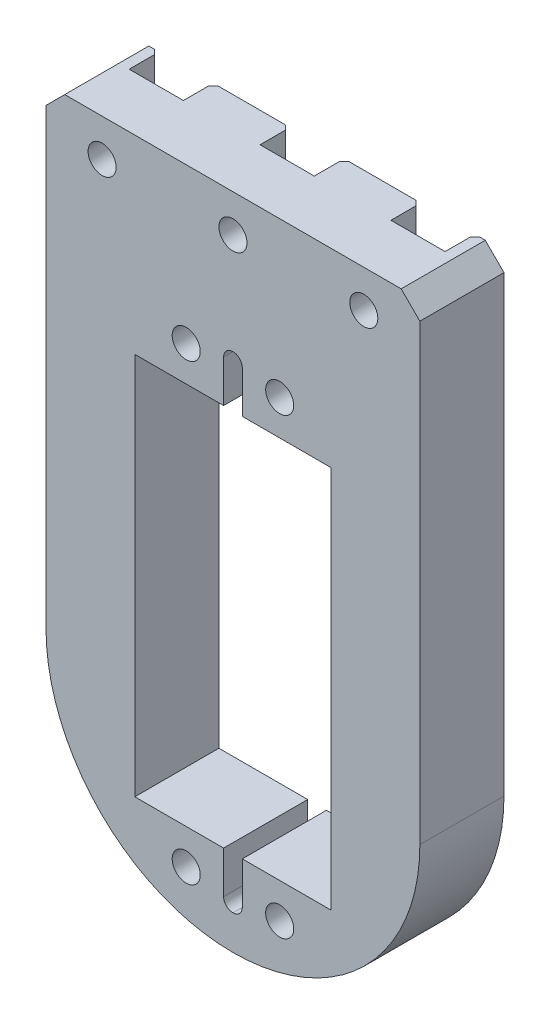
SolidWorks part; units mm, degrees
ref_plane "前视基准面" through (0, 0, 0) normal (0, 0, 1) x (1, 0, 0)
ref_plane "上视基准面" through (0, 0, 0) normal (0, 1, 0) x (1, 0, 0)
ref_plane "右视基准面" through (0, 0, 0) normal (1, 0, 0) x (0, 0, -1)
other "Configuration Table"
sketch "草图1" plane through (0, 0, 0) normal (0, 0, 1) x (1, 0, 0)
  line L1 (0, 0.5) -> (40, 0.5)
  line L2 (0, 0.5) -> (0, -70)
  line L3 (0, -70) -> (40, -70)
  line L4 (40, 0.5) -> (40, -70)
  dimension "D1" = 40
  dimension "D2" = 70.5
extrude "凸台-拉伸1" add sketch "草图1" along normal blind 9
chamfer "倒角1" distance 2 angle 45 2 edges at (40, 0.5, 4.5) (0, 0.5, 4.5)
fillet "圆角3" radius 20 2 edges at (0, -70, 4.5) (40, -70, 4.5)
sketch "草图2" plane through (0, 0, 0) normal (0, 0, -1) x (-1, 0, 0)
  line L0 (0, -1.5) -> (0, -50) construction
  line L1 (-30.5, -19.82) -> (-9.5, -19.82)
  line L2 (-30.5, -19.82) -> (-30.5, -60.82)
  line L3 (-30.5, -60.82) -> (-9.5, -60.82)
  line L4 (-9.5, -19.82) -> (-9.5, -60.82)
  line L5 (-30.5, -19.82) -> (-9.5, -60.82) construction
  line L6 (-30.5, -60.82) -> (-9.5, -19.82) construction
  point P0 (-20, -40.32)
  dimension "D1" = 21
  dimension "D2" = 41
  dimension "D3" = 20
  dimension "D4" = 29.68
extrude "切除-拉伸1" cut sketch "草图2" against normal blind 10
sketch "草图3" plane through (0, 0, 9) normal (0, 0, 1) x (1, 0, 0)
  line L0 (19, -14.32) -> (21, -14.32)
  line L1 (19, -14.32) -> (19, -19.82)
  line L2 (19, -19.82) -> (21, -19.82)
  line L3 (21, -14.32) -> (21, -19.82)
  line L4 (19, -14.32) -> (21, -19.82) construction
  line L5 (19, -19.82) -> (21, -14.32) construction
  line L6 (19, -60.82) -> (19, -66.32)
  line L7 (19, -60.82) -> (21, -60.82)
  line L8 (21, -60.82) -> (21, -66.32)
  line L9 (19, -66.32) -> (21, -66.32)
  line L10 (30.5, -19.82) -> (9.5, -19.82) construction
  line L11 (9.5, -19.82) -> (9.5, -60.82) construction
  line L12 (9.5, -60.82) -> (30.5, -60.82) construction
  point P0 (20, -17.07)
  dimension "D1" = 2
  dimension "D2" = 0
  dimension "D3" = 10.5
  dimension "D4" = 0
  dimension "D5" = 9.5
  dimension "D6" = 5.5
  dimension "D7" = 5.5
  dimension "D8" = 2
extrude "切除-拉伸2" cut sketch "草图3" against normal blind 10
sketch "草图4" plane through (0, 0, 0) normal (0, 0, -1) x (-1, 0, 0)
  line L0 (-21, -19.82) -> (-21, -14.32) construction
  line L1 (-21, -19.82) -> (-30.5, -19.82) construction
  circle A0 centre (-25, -16.07) radius 1.5
  circle A1 centre (-15, -16.07) radius 1.5
  circle A2 centre (-25, -64.57) radius 1.5
  circle A3 centre (-15, -64.57) radius 1.5
  dimension "D1" = 3
  dimension "D2" = 4
  dimension "D3" = 3.75
  dimension "D4" = 2
  dimension "D5" = 2
extrude "切除-拉伸3" cut sketch "草图4" against normal blind 10
sketch "草图5" plane through (0, 0, 0) normal (0, 0, -1) x (-1, 0, 0)
  line L0 (-38, 0.5) -> (-2, 0.5) construction
  line L1 (-40, -50) -> (-40, -1.5) construction
  circle A0 centre (-34, -3.5) radius 1.5
  circle A1 centre (-20, -3.5) radius 1.5
  circle A2 centre (-6, -3.5) radius 1.5
  dimension "D1" = 3
  dimension "D3" = 6
  dimension "D6" = 14
  dimension "D7" = 14
  dimension "D2" = 4
  dimension "D4" = 2
  dimension "D5" = 2
extrude "切除-拉伸4" cut sketch "草图5" against normal blind 10
fillet "圆角4" radius 1 4 edges at (21, -66.32, 4.5) (19, -66.32, 4.5) (21, -14.32, 4.5) (19, -14.32, 4.5)
sketch "草图7" plane through (0, 0, 0) normal (0, 0, -1) x (-1, 0, 0)
  line L2 (-36.9, -3.5) -> (-36.9, 0.5)
  line L3 (-36.9, 0.5) -> (-31.1, 0.5)
  line L4 (-31.1, -3.5) -> (-31.1, 0.5)
  line L5 (-17.1, -3.5) -> (-17.1, 0.5)
  line L6 (-22.9, 0.5) -> (-17.1, 0.5)
  line L7 (-22.9, -3.5) -> (-22.9, 0.5)
  line L8 (-3.1, -3.5) -> (-3.1, 0.5)
  line L9 (-8.9, 0.5) -> (-3.1, 0.5)
  line L10 (-8.9, -3.5) -> (-8.9, 0.5)
  line L11 (-38, 0.5) -> (-2, 0.5) construction
  arc A0 (-36.9, -3.5) -> (-31.1, -3.5) centre (-34, -3.5) ccw
  arc A1 (-22.9, -3.5) -> (-17.1, -3.5) centre (-20, -3.5) ccw
  arc A2 (-8.9, -3.5) -> (-3.1, -3.5) centre (-6, -3.5) ccw
  circle A3 centre (-20, -3.5) radius 1.5 construction
  circle A4 centre (-6, -3.5) radius 1.5 construction
  dimension "D1" = 5.8
  dimension "D6" = 2.9
  dimension "D11" = 2.9
  dimension "D2" = 5.8
  dimension "D4" = 14
  dimension "D5" = 5.8
  dimension "D3" = 14
  dimension "D7" = 5.8
  dimension "D8" = 4
  dimension "D9" = 4
  dimension "D10" = 4
  dimension "D12" = 8.2
extrude "切除-拉伸5" cut sketch "草图7" against normal blind 3.2
chamfer "倒角2" distance 0.5 angle 45 13 edges at (13.5, -64.57, 0) (23.5, -64.57, 0) (13.5, -16.07, 0) (23.5, -16.07, 0) (3.1, -1.5, 0) (6, -6.4, 0) (8.9, -1.5, 0) (17.1, -1.5, 0) (20, -6.4, 0) (22.9, -1.5, 0) (31.1, -1.5, 0) (34, -6.4, 0) (36.9, -1.5, 0)
